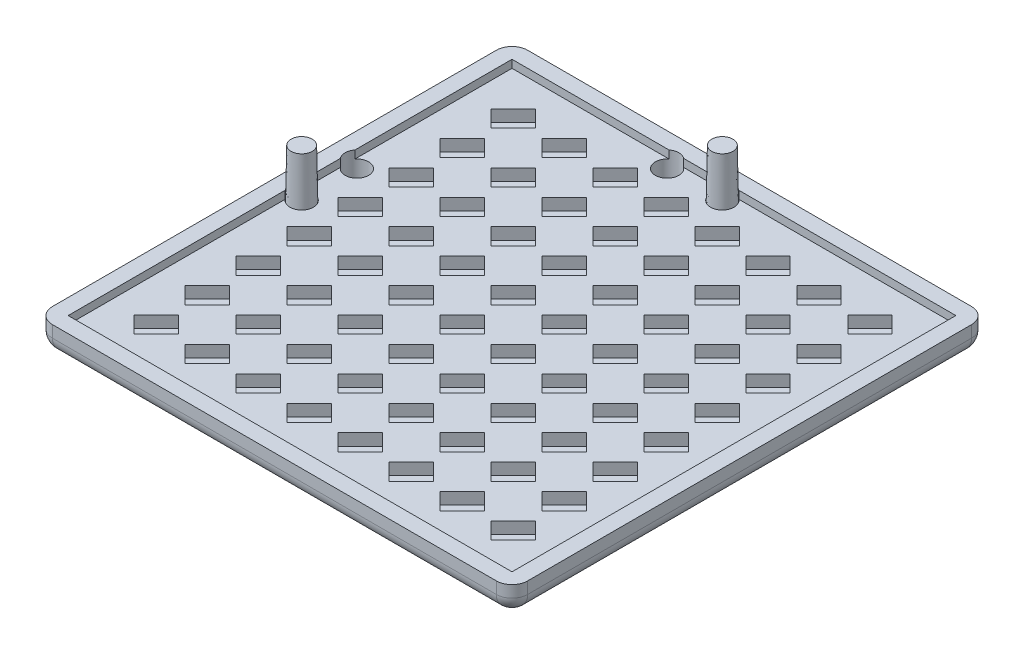
SolidWorks part; units mm, degrees
ref_plane "Front Plane" through (0, 0, 0) normal (0, 0, 1) x (1, 0, 0)
ref_plane "Top Plane" through (0, 0, 0) normal (0, 1, 0) x (1, 0, 0)
ref_plane "Right Plane" through (0, 0, 0) normal (1, 0, 0) x (0, 0, -1)
sketch "Sketch1" plane through (0, 0, 0) normal (0, 1, 0) x (1, 0, 0)
  line L1 (-30.3, -30.3) -> (30.3, -30.3)
  line L2 (-30.3, -30.3) -> (-30.3, 30.3)
  line L3 (-30.3, 30.3) -> (30.3, 30.3)
  line L4 (30.3, -30.3) -> (30.3, 30.3)
  line L5 (-30.3, -30.3) -> (30.3, 30.3) construction
  line L6 (-30.3, 30.3) -> (30.3, -30.3) construction
  point P0 (0, 0)
  dimension "D1" = 60.6
  dimension "D2" = 60.6
extrude "Boss-Extrude1" add sketch "Sketch1" along normal blind 3.5
sketch "led" plane through (0, 0, 0) normal (0, -1, 0) x (1, 0, 0)
  line L0 (30.3, -30.3) -> (-30.3, 30.3) construction
  line L1 (-30.3, 30.3) -> (-30.3, -30.3) construction
  line L2 (-30.3, -30.3) -> (30.3, 30.3) construction
  line L3 (22.4716, -20.3503) -> (25.3, -23.1787)
  line L4 (22.4716, -20.3503) -> (20.3503, -22.4716)
  line L5 (25.3, -23.1787) -> (23.1787, -25.3)
  line L6 (20.3503, -22.4716) -> (23.1787, -25.3)
  line L7 (22.4716, -20.3503) -> (23.1787, -25.3) construction
  line L8 (25.3, -23.1787) -> (20.3503, -22.4716) construction
  line L11 (30.3, 30.3) -> (30.3, -30.3) construction
  line L13 (13.8503, -22.4716) -> (16.6787, -25.3)
  line L14 (15.9716, -20.3503) -> (18.8, -23.1787)
  line L15 (15.9716, -20.3503) -> (13.8503, -22.4716)
  line L16 (18.8, -23.1787) -> (16.6787, -25.3)
  line L17 (7.3503, -22.4716) -> (10.1787, -25.3)
  line L18 (9.4716, -20.3503) -> (12.3, -23.1787)
  line L19 (9.4716, -20.3503) -> (7.3503, -22.4716)
  line L20 (12.3, -23.1787) -> (10.1787, -25.3)
  line L21 (0.8503, -22.4716) -> (3.6787, -25.3)
  line L22 (2.9716, -20.3503) -> (5.8, -23.1787)
  line L23 (2.9716, -20.3503) -> (0.8503, -22.4716)
  line L24 (5.8, -23.1787) -> (3.6787, -25.3)
  line L25 (-5.6497, -22.4716) -> (-2.8213, -25.3)
  line L26 (-3.5284, -20.3503) -> (-0.7, -23.1787)
  line L27 (-3.5284, -20.3503) -> (-5.6497, -22.4716)
  line L28 (-0.7, -23.1787) -> (-2.8213, -25.3)
  line L29 (-12.1497, -22.4716) -> (-9.3213, -25.3)
  line L30 (-10.0284, -20.3503) -> (-7.2, -23.1787)
  line L31 (-10.0284, -20.3503) -> (-12.1497, -22.4716)
  line L32 (-7.2, -23.1787) -> (-9.3213, -25.3)
  line L33 (-18.6497, -22.4716) -> (-15.8213, -25.3)
  line L34 (-16.5284, -20.3503) -> (-13.7, -23.1787)
  line L35 (-16.5284, -20.3503) -> (-18.6497, -22.4716)
  line L36 (-13.7, -23.1787) -> (-15.8213, -25.3)
  line L37 (-25.1497, -22.4716) -> (-22.3213, -25.3)
  line L38 (-23.0284, -20.3503) -> (-20.2, -23.1787)
  line L39 (-23.0284, -20.3503) -> (-25.1497, -22.4716)
  line L40 (-20.2, -23.1787) -> (-22.3213, -25.3)
  line L41 (13.8503, -15.9716) -> (16.6787, -18.8)
  line L42 (15.9716, -13.8503) -> (18.8, -16.6787)
  line L43 (15.9716, -13.8503) -> (13.8503, -15.9716)
  line L44 (18.8, -16.6787) -> (16.6787, -18.8)
  line L45 (7.3503, -15.9716) -> (10.1787, -18.8)
  line L46 (9.4716, -13.8503) -> (12.3, -16.6787)
  line L47 (9.4716, -13.8503) -> (7.3503, -15.9716)
  line L48 (12.3, -16.6787) -> (10.1787, -18.8)
  line L49 (0.8503, -15.9716) -> (3.6787, -18.8)
  line L50 (2.9716, -13.8503) -> (5.8, -16.6787)
  line L51 (2.9716, -13.8503) -> (0.8503, -15.9716)
  line L52 (5.8, -16.6787) -> (3.6787, -18.8)
  line L53 (-5.6497, -15.9716) -> (-2.8213, -18.8)
  line L54 (-3.5284, -13.8503) -> (-0.7, -16.6787)
  line L55 (-3.5284, -13.8503) -> (-5.6497, -15.9716)
  line L56 (-0.7, -16.6787) -> (-2.8213, -18.8)
  line L57 (-12.1497, -15.9716) -> (-9.3213, -18.8)
  line L58 (-10.0284, -13.8503) -> (-7.2, -16.6787)
  line L59 (-10.0284, -13.8503) -> (-12.1497, -15.9716)
  line L60 (-7.2, -16.6787) -> (-9.3213, -18.8)
  line L61 (-18.6497, -15.9716) -> (-15.8213, -18.8)
  line L62 (-16.5284, -13.8503) -> (-13.7, -16.6787)
  line L63 (-16.5284, -13.8503) -> (-18.6497, -15.9716)
  line L64 (-13.7, -16.6787) -> (-15.8213, -18.8)
  line L65 (-25.1497, -15.9716) -> (-22.3213, -18.8)
  line L66 (-23.0284, -13.8503) -> (-20.2, -16.6787)
  line L67 (-23.0284, -13.8503) -> (-25.1497, -15.9716)
  line L68 (-20.2, -16.6787) -> (-22.3213, -18.8)
  line L69 (13.8503, -9.4716) -> (16.6787, -12.3)
  line L70 (15.9716, -7.3503) -> (18.8, -10.1787)
  line L71 (15.9716, -7.3503) -> (13.8503, -9.4716)
  line L72 (18.8, -10.1787) -> (16.6787, -12.3)
  line L73 (7.3503, -9.4716) -> (10.1787, -12.3)
  line L74 (9.4716, -7.3503) -> (12.3, -10.1787)
  line L75 (9.4716, -7.3503) -> (7.3503, -9.4716)
  line L76 (12.3, -10.1787) -> (10.1787, -12.3)
  line L77 (0.8503, -9.4716) -> (3.6787, -12.3)
  line L78 (2.9716, -7.3503) -> (5.8, -10.1787)
  line L79 (2.9716, -7.3503) -> (0.8503, -9.4716)
  line L80 (5.8, -10.1787) -> (3.6787, -12.3)
  line L81 (-5.6497, -9.4716) -> (-2.8213, -12.3)
  line L82 (-3.5284, -7.3503) -> (-0.7, -10.1787)
  line L83 (-3.5284, -7.3503) -> (-5.6497, -9.4716)
  line L84 (-0.7, -10.1787) -> (-2.8213, -12.3)
  line L85 (-12.1497, -9.4716) -> (-9.3213, -12.3)
  line L86 (-10.0284, -7.3503) -> (-7.2, -10.1787)
  line L87 (-10.0284, -7.3503) -> (-12.1497, -9.4716)
  line L88 (-7.2, -10.1787) -> (-9.3213, -12.3)
  line L89 (-18.6497, -9.4716) -> (-15.8213, -12.3)
  line L90 (-16.5284, -7.3503) -> (-13.7, -10.1787)
  line L91 (-16.5284, -7.3503) -> (-18.6497, -9.4716)
  line L92 (-13.7, -10.1787) -> (-15.8213, -12.3)
  line L93 (-25.1497, -9.4716) -> (-22.3213, -12.3)
  line L94 (-23.0284, -7.3503) -> (-20.2, -10.1787)
  line L95 (-23.0284, -7.3503) -> (-25.1497, -9.4716)
  line L96 (-20.2, -10.1787) -> (-22.3213, -12.3)
  line L97 (13.8503, -2.9716) -> (16.6787, -5.8)
  line L98 (15.9716, -0.8503) -> (18.8, -3.6787)
  line L99 (15.9716, -0.8503) -> (13.8503, -2.9716)
  line L100 (18.8, -3.6787) -> (16.6787, -5.8)
  line L101 (7.3503, -2.9716) -> (10.1787, -5.8)
  line L102 (9.4716, -0.8503) -> (12.3, -3.6787)
  line L103 (9.4716, -0.8503) -> (7.3503, -2.9716)
  line L104 (12.3, -3.6787) -> (10.1787, -5.8)
  line L105 (0.8503, -2.9716) -> (3.6787, -5.8)
  line L106 (2.9716, -0.8503) -> (5.8, -3.6787)
  line L107 (2.9716, -0.8503) -> (0.8503, -2.9716)
  line L108 (5.8, -3.6787) -> (3.6787, -5.8)
  line L109 (-5.6497, -2.9716) -> (-2.8213, -5.8)
  line L110 (-3.5284, -0.8503) -> (-0.7, -3.6787)
  line L111 (-3.5284, -0.8503) -> (-5.6497, -2.9716)
  line L112 (-0.7, -3.6787) -> (-2.8213, -5.8)
  line L113 (-12.1497, -2.9716) -> (-9.3213, -5.8)
  line L114 (-10.0284, -0.8503) -> (-7.2, -3.6787)
  line L115 (-10.0284, -0.8503) -> (-12.1497, -2.9716)
  line L116 (-7.2, -3.6787) -> (-9.3213, -5.8)
  line L117 (-18.6497, -2.9716) -> (-15.8213, -5.8)
  line L118 (-16.5284, -0.8503) -> (-13.7, -3.6787)
  line L119 (-16.5284, -0.8503) -> (-18.6497, -2.9716)
  line L120 (-13.7, -3.6787) -> (-15.8213, -5.8)
  line L121 (-25.1497, -2.9716) -> (-22.3213, -5.8)
  line L122 (-23.0284, -0.8503) -> (-20.2, -3.6787)
  line L123 (-23.0284, -0.8503) -> (-25.1497, -2.9716)
  line L124 (-20.2, -3.6787) -> (-22.3213, -5.8)
  line L125 (13.8503, 3.5284) -> (16.6787, 0.7)
  line L126 (15.9716, 5.6497) -> (18.8, 2.8213)
  line L127 (15.9716, 5.6497) -> (13.8503, 3.5284)
  line L128 (18.8, 2.8213) -> (16.6787, 0.7)
  line L129 (7.3503, 3.5284) -> (10.1787, 0.7)
  line L130 (9.4716, 5.6497) -> (12.3, 2.8213)
  line L131 (9.4716, 5.6497) -> (7.3503, 3.5284)
  line L132 (12.3, 2.8213) -> (10.1787, 0.7)
  line L133 (0.8503, 3.5284) -> (3.6787, 0.7)
  line L134 (2.9716, 5.6497) -> (5.8, 2.8213)
  line L135 (2.9716, 5.6497) -> (0.8503, 3.5284)
  line L136 (5.8, 2.8213) -> (3.6787, 0.7)
  line L137 (-5.6497, 3.5284) -> (-2.8213, 0.7)
  line L138 (-3.5284, 5.6497) -> (-0.7, 2.8213)
  line L139 (-3.5284, 5.6497) -> (-5.6497, 3.5284)
  line L140 (-0.7, 2.8213) -> (-2.8213, 0.7)
  line L141 (-12.1497, 3.5284) -> (-9.3213, 0.7)
  line L142 (-10.0284, 5.6497) -> (-7.2, 2.8213)
  line L143 (-10.0284, 5.6497) -> (-12.1497, 3.5284)
  line L144 (-7.2, 2.8213) -> (-9.3213, 0.7)
  line L145 (-18.6497, 3.5284) -> (-15.8213, 0.7)
  line L146 (-16.5284, 5.6497) -> (-13.7, 2.8213)
  line L147 (-16.5284, 5.6497) -> (-18.6497, 3.5284)
  line L148 (-13.7, 2.8213) -> (-15.8213, 0.7)
  line L149 (-25.1497, 3.5284) -> (-22.3213, 0.7)
  line L150 (-23.0284, 5.6497) -> (-20.2, 2.8213)
  line L151 (-23.0284, 5.6497) -> (-25.1497, 3.5284)
  line L152 (-20.2, 2.8213) -> (-22.3213, 0.7)
  line L153 (13.8503, 10.0284) -> (16.6787, 7.2)
  line L154 (15.9716, 12.1497) -> (18.8, 9.3213)
  line L155 (15.9716, 12.1497) -> (13.8503, 10.0284)
  line L156 (18.8, 9.3213) -> (16.6787, 7.2)
  line L157 (7.3503, 10.0284) -> (10.1787, 7.2)
  line L158 (9.4716, 12.1497) -> (12.3, 9.3213)
  line L159 (9.4716, 12.1497) -> (7.3503, 10.0284)
  line L160 (12.3, 9.3213) -> (10.1787, 7.2)
  line L161 (0.8503, 10.0284) -> (3.6787, 7.2)
  line L162 (2.9716, 12.1497) -> (5.8, 9.3213)
  line L163 (2.9716, 12.1497) -> (0.8503, 10.0284)
  line L164 (5.8, 9.3213) -> (3.6787, 7.2)
  line L165 (-5.6497, 10.0284) -> (-2.8213, 7.2)
  line L166 (-3.5284, 12.1497) -> (-0.7, 9.3213)
  line L167 (-3.5284, 12.1497) -> (-5.6497, 10.0284)
  line L168 (-0.7, 9.3213) -> (-2.8213, 7.2)
  line L169 (-12.1497, 10.0284) -> (-9.3213, 7.2)
  line L170 (-10.0284, 12.1497) -> (-7.2, 9.3213)
  line L171 (-10.0284, 12.1497) -> (-12.1497, 10.0284)
  line L172 (-7.2, 9.3213) -> (-9.3213, 7.2)
  line L173 (-18.6497, 10.0284) -> (-15.8213, 7.2)
  line L174 (-16.5284, 12.1497) -> (-13.7, 9.3213)
  line L175 (-16.5284, 12.1497) -> (-18.6497, 10.0284)
  line L176 (-13.7, 9.3213) -> (-15.8213, 7.2)
  line L177 (-25.1497, 10.0284) -> (-22.3213, 7.2)
  line L178 (-23.0284, 12.1497) -> (-20.2, 9.3213)
  line L179 (-23.0284, 12.1497) -> (-25.1497, 10.0284)
  line L180 (-20.2, 9.3213) -> (-22.3213, 7.2)
  line L181 (13.8503, 16.5284) -> (16.6787, 13.7)
  line L182 (15.9716, 18.6497) -> (18.8, 15.8213)
  line L183 (15.9716, 18.6497) -> (13.8503, 16.5284)
  line L184 (18.8, 15.8213) -> (16.6787, 13.7)
  line L185 (7.3503, 16.5284) -> (10.1787, 13.7)
  line L186 (9.4716, 18.6497) -> (12.3, 15.8213)
  line L187 (9.4716, 18.6497) -> (7.3503, 16.5284)
  line L188 (12.3, 15.8213) -> (10.1787, 13.7)
  line L189 (0.8503, 16.5284) -> (3.6787, 13.7)
  line L190 (2.9716, 18.6497) -> (5.8, 15.8213)
  line L191 (2.9716, 18.6497) -> (0.8503, 16.5284)
  line L192 (5.8, 15.8213) -> (3.6787, 13.7)
  line L193 (-5.6497, 16.5284) -> (-2.8213, 13.7)
  line L194 (-3.5284, 18.6497) -> (-0.7, 15.8213)
  line L195 (-3.5284, 18.6497) -> (-5.6497, 16.5284)
  line L196 (-0.7, 15.8213) -> (-2.8213, 13.7)
  line L197 (-12.1497, 16.5284) -> (-9.3213, 13.7)
  line L198 (-10.0284, 18.6497) -> (-7.2, 15.8213)
  line L199 (-10.0284, 18.6497) -> (-12.1497, 16.5284)
  line L200 (-7.2, 15.8213) -> (-9.3213, 13.7)
  line L201 (-18.6497, 16.5284) -> (-15.8213, 13.7)
  line L202 (-16.5284, 18.6497) -> (-13.7, 15.8213)
  line L203 (-16.5284, 18.6497) -> (-18.6497, 16.5284)
  line L204 (-13.7, 15.8213) -> (-15.8213, 13.7)
  line L205 (-25.1497, 16.5284) -> (-22.3213, 13.7)
  line L206 (-23.0284, 18.6497) -> (-20.2, 15.8213)
  line L207 (-23.0284, 18.6497) -> (-25.1497, 16.5284)
  line L208 (-20.2, 15.8213) -> (-22.3213, 13.7)
  line L209 (13.8503, 23.0284) -> (16.6787, 20.2)
  line L210 (15.9716, 25.1497) -> (18.8, 22.3213)
  line L211 (15.9716, 25.1497) -> (13.8503, 23.0284)
  line L212 (18.8, 22.3213) -> (16.6787, 20.2)
  line L213 (7.3503, 23.0284) -> (10.1787, 20.2)
  line L214 (9.4716, 25.1497) -> (12.3, 22.3213)
  line L215 (9.4716, 25.1497) -> (7.3503, 23.0284)
  line L216 (12.3, 22.3213) -> (10.1787, 20.2)
  line L217 (0.8503, 23.0284) -> (3.6787, 20.2)
  line L218 (2.9716, 25.1497) -> (5.8, 22.3213)
  line L219 (2.9716, 25.1497) -> (0.8503, 23.0284)
  line L220 (5.8, 22.3213) -> (3.6787, 20.2)
  line L221 (-5.6497, 23.0284) -> (-2.8213, 20.2)
  line L222 (-3.5284, 25.1497) -> (-0.7, 22.3213)
  line L223 (-3.5284, 25.1497) -> (-5.6497, 23.0284)
  line L224 (-0.7, 22.3213) -> (-2.8213, 20.2)
  line L225 (-12.1497, 23.0284) -> (-9.3213, 20.2)
  line L226 (-10.0284, 25.1497) -> (-7.2, 22.3213)
  line L227 (-10.0284, 25.1497) -> (-12.1497, 23.0284)
  line L228 (-7.2, 22.3213) -> (-9.3213, 20.2)
  line L229 (-18.6497, 23.0284) -> (-15.8213, 20.2)
  line L230 (-16.5284, 25.1497) -> (-13.7, 22.3213)
  line L231 (-16.5284, 25.1497) -> (-18.6497, 23.0284)
  line L232 (-13.7, 22.3213) -> (-15.8213, 20.2)
  line L233 (-25.1497, 23.0284) -> (-22.3213, 20.2)
  line L234 (-23.0284, 25.1497) -> (-20.2, 22.3213)
  line L235 (-23.0284, 25.1497) -> (-25.1497, 23.0284)
  line L236 (-20.2, 22.3213) -> (-22.3213, 20.2)
  line L237 (20.3503, -15.9716) -> (23.1787, -18.8)
  line L238 (22.4716, -13.8503) -> (25.3, -16.6787)
  line L239 (22.4716, -13.8503) -> (20.3503, -15.9716)
  line L240 (25.3, -16.6787) -> (23.1787, -18.8)
  line L241 (20.3503, -9.4716) -> (23.1787, -12.3)
  line L242 (22.4716, -7.3503) -> (25.3, -10.1787)
  line L243 (22.4716, -7.3503) -> (20.3503, -9.4716)
  line L244 (25.3, -10.1787) -> (23.1787, -12.3)
  line L245 (20.3503, -2.9716) -> (23.1787, -5.8)
  line L246 (22.4716, -0.8503) -> (25.3, -3.6787)
  line L247 (22.4716, -0.8503) -> (20.3503, -2.9716)
  line L248 (25.3, -3.6787) -> (23.1787, -5.8)
  line L249 (20.3503, 3.5284) -> (23.1787, 0.7)
  line L250 (22.4716, 5.6497) -> (25.3, 2.8213)
  line L251 (22.4716, 5.6497) -> (20.3503, 3.5284)
  line L252 (25.3, 2.8213) -> (23.1787, 0.7)
  line L253 (20.3503, 10.0284) -> (23.1787, 7.2)
  line L254 (22.4716, 12.1497) -> (25.3, 9.3213)
  line L255 (22.4716, 12.1497) -> (20.3503, 10.0284)
  line L256 (25.3, 9.3213) -> (23.1787, 7.2)
  line L257 (20.3503, 16.5284) -> (23.1787, 13.7)
  line L258 (22.4716, 18.6497) -> (25.3, 15.8213)
  line L259 (22.4716, 18.6497) -> (20.3503, 16.5284)
  line L260 (25.3, 15.8213) -> (23.1787, 13.7)
  line L261 (20.3503, 23.0284) -> (23.1787, 20.2)
  line L262 (22.4716, 25.1497) -> (25.3, 22.3213)
  line L263 (22.4716, 25.1497) -> (20.3503, 23.0284)
  line L264 (25.3, 22.3213) -> (23.1787, 20.2)
  point P9 (22.8251, -22.8251)
  dimension "D1" = 4
  dimension "D2" = 3
  dimension "D3" = 5
  dimension "D4" = 8
  dimension "D5" = 8
extrude "Cut-Extrude1" cut sketch "led" against normal through all from offset 1 offset against normal yes
sketch "Sketch3" plane through (0, 3.5, 0) normal (0, 1, 0) x (1, 0, 0)
  line L0 (30.3, 30.3) -> (-30.3, 30.3) construction
  line L1 (28.3, -28.3) -> (-28.3, -28.3)
  line L2 (28.3, -28.3) -> (28.3, 28.3)
  line L3 (28.3, 28.3) -> (-28.3, 28.3)
  line L4 (-28.3, -28.3) -> (-28.3, 28.3)
  line L5 (28.3, -28.3) -> (-28.3, 28.3) construction
  line L6 (28.3, 28.3) -> (-28.3, -28.3) construction
  line L7 (-30.3, 30.3) -> (-30.3, -30.3) construction
  point P0 (0, 0)
  dimension "D1" = 2
  dimension "D2" = 2
extrude "Cut-Extrude2" cut sketch "Sketch3" along normal through all from offset 1 offset against normal yes
sketch "Sketch4" plane through (0, 3.5, 0) normal (0, 1, 0) x (1, 0, 0)
  line L0 (-30.3, 30.3) -> (30.3, -30.3) construction
  line L2 (30.3, 30.3) -> (-30.3, 30.3) construction
  line L3 (-0.3, 27.12) -> (-7.34, 27.12) construction
  line L4 (-30.3, 30.3) -> (-30.3, -30.3) construction
  circle A0 centre (-0.3, 27.12) radius 1.5
  circle A1 centre (-7.34, 27.12) radius 1.5
  circle A2 centre (-27.12, 7.34) radius 1.5
  circle A3 centre (-27.12, 0.3) radius 1.5
  dimension "D1" = 3
  dimension "D2" = 3
  dimension "D3" = 30
  dimension "D4" = 7.04
  dimension "D5" = 3.18
extrude "Cut-Extrude3" cut sketch "Sketch4" against normal through all
sketch "Sketch5" plane through (0, 3.5, 0) normal (0, 1, 0) x (1, 0, 0)
  line L0 (-30.3, 30.3) -> (30.3, -30.3) construction
  circle A0 centre (-27.12, 0.3) radius 1.5
  circle A1 centre (-27.12, 0.3) radius 1.5 construction
  circle A2 centre (-0.3, 27.12) radius 1.5
  dimension "D1" = 3
extrude "Boss-Extrude3" add sketch "Sketch5" along normal blind 8.6 draft 1 from surface separate body starting at face at (-0.3, 0, -25.62)
fillet "Fillet3" radius 2 4 edges at (-30.3, 1.75, 30.3) (-30.3, 1.75, -30.3) (30.3, 1.75, -30.3) (30.3, 1.75, 30.3)
fillet "Fillet4" radius 2 8 edges at (-29.7142, 0, 29.7142) (-30.3, 0, 0) (-29.7142, 0, -29.7142) (0, 0, -30.3) (29.7142, 0, -29.7142) (30.3, 0, 0) (29.7142, 0, 29.7142) (0, 0, 30.3)
